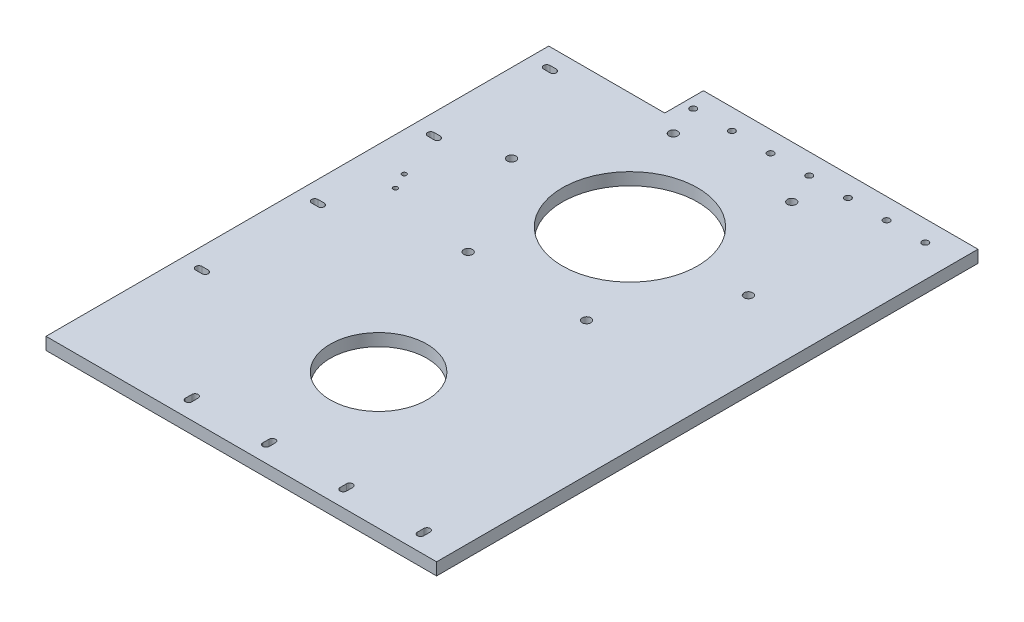
SolidWorks part; units mm, degrees
ref_plane "Front Plane" through (0, 0, 0) normal (0, 0, 1) x (1, 0, 0)
ref_plane "Top Plane" through (0, 0, 0) normal (0, 1, 0) x (1, 0, 0)
ref_plane "Right Plane" through (0, 0, 0) normal (1, 0, 0) x (0, 0, -1)
sketch "Sketch1" plane through (0, 0, 0) normal (0, 1, 0) x (1, 0, 0)
  line L3 (-71, 140) -> (71, 140)
  line L4 (71, -140) -> (71, 140)
  line L5 (0, 140) -> (0, -135) construction
  line L6 (0, 0) -> (71, 0) construction
  line L10 (-71, 140) -> (-71, 120)
  line L11 (-71, 120) -> (-131, 120)
  line L12 (-131, 120) -> (-131, -140)
  line L13 (-131, -140) -> (71, -140)
  point P0 (0, 0)
  dimension "D1" = 280
  dimension "D2" = 20
  dimension "D3" = 202
  dimension "D4" = 60
extrude "Boss-Extrude1" add sketch "Sketch1" along normal blind 6.35
sketch "Sketch2" plane through (0, 6.35, 0) normal (0, 1, 0) x (1, 0, 0)
  line L1 (0, 140) -> (0, -140) construction
  line L2 (71, 140) -> (-71, 140) construction
  line L3 (-131, -140) -> (71, -140) construction
  circle A0 centre (0, -65) radius 41.5 construction
  circle A1 centre (0, -23.5) radius 2.25
  circle A2 centre (29.3449, -35.6551) radius 2.25
  circle A3 centre (41.5, -65) radius 2.25
  circle A4 centre (29.3449, -94.3449) radius 2.25
  circle A5 centre (0, -106.5) radius 2.25
  circle A6 centre (-29.3449, -94.3449) radius 2.25
  circle A7 centre (-41.5, -65) radius 2.25
  circle A8 centre (-29.3449, -35.6551) radius 2.25
  circle A9 centre (0, -65) radius 80 construction
  circle A10 centre (0, -65) radius 30
  point P22 (0, -65)
  dimension "D1" = 83
  dimension "D2" = 4.5
  dimension "D4" = 160
  dimension "D6" = 60
  dimension "D5" = 75
  dimension "D3" = 8
extrude "Cut-Extrude1" [suppressed] cut sketch "Sketch2" against normal through all
sketch "Sketch6" [suppressed] plane through (0, 6.35, 0) normal (0, 1, 0) x (1, 0, 0)
  line L0 (0, -65) -> (-38.9712, -46.8274) construction
  line L1 (0, -65) -> (0, -23.5) construction
  line L2 (-40.9787, -51.1324) -> (-36.9638, -42.5225) construction
  line L3 (-36.9638, -42.5225) -> (-27.9007, -46.7486) construction
  circle A0 centre (0, -65) radius 30 construction
  circle A1 centre (-36.9638, -42.5225) radius 0.85
  circle A2 centre (-40.9787, -51.1324) radius 0.85
  circle A5 centre (-29.9082, -51.0536) radius 0.85
  point P7 (-38.9712, -46.8274)
  dimension "D4" = 1.7
  dimension "D5" = 10
  dimension "D7" = 10
  dimension "D6" = 1.7
  dimension "D1" = 43
  dimension "D2" = 9.5
  dimension "D3" = 65
extrude "Cut-Extrude5" [suppressed] cut sketch "Sketch6" against normal through all
sketch "Sketch8" [suppressed] plane through (0, 6.35, 0) normal (0, 1, 0) x (1, 0, 0)
  line L1 (71, 140) -> (-71, 140) construction
  line L2 (65, -20.6305) -> (65, 140) construction
  line L3 (71, -140) -> (71, 140) construction
  line L5 (45, 41.8036) -> (45, 140) construction
  circle A0 centre (0, 65) radius 25
  circle A1 centre (0, -65) radius 30 construction
  dimension "D1" = 130
  dimension "D2" = 50
  dimension "D3" = 6
  dimension "D4" = 20
extrude "Cut-Extrude9" [suppressed] cut sketch "Sketch8" against normal through all
sketch "Sketch9" plane through (0, 0, 0) normal (0, -1, 0) x (-1, 0, 0)
  circle A1 centre (45.6, 129.325) radius 1.65
  circle A2 centre (5.6, 129.325) radius 1.65
  circle A3 centre (-34.4, 129.325) radius 1.65
  circle A4 centre (65.6, 129.325) radius 1.65
  circle A5 centre (25.6, 129.325) radius 1.65
  circle A6 centre (-14.4, 129.325) radius 1.65
  circle A7 centre (-54.4, 129.325) radius 1.65
extrude "Cut-Extrude10" cut sketch "Sketch9" against normal blind 30
sketch "Sketch10" plane through (0, 0, 0) normal (0, -1, 0) x (1, 0, 0)
  line L0 (-121.975, 10) -> (-118.675, 10) construction
  line L3 (-121.975, 11.65) -> (-118.675, 11.65)
  line L4 (-121.975, 8.35) -> (-118.675, 8.35)
  line L5 (-121.975, 70) -> (-118.675, 70) construction
  line L6 (-121.975, 71.65) -> (-118.675, 71.65)
  line L7 (-121.975, 68.35) -> (-118.675, 68.35)
  line L8 (-121.975, -50) -> (-118.675, -50) construction
  line L9 (-121.975, -48.35) -> (-118.675, -48.35)
  line L10 (-121.975, -51.65) -> (-118.675, -51.65)
  line L11 (-121.975, -110) -> (-118.675, -110) construction
  line L12 (-121.975, -108.35) -> (-118.675, -108.35)
  line L13 (-121.975, -111.65) -> (-118.675, -111.65)
  circle A0 centre (-120.325, -110) radius 1.65
  circle A1 centre (-120.325, -50) radius 1.65
  circle A2 centre (-120.325, 10) radius 1.65
  circle A3 centre (-120.325, 70) radius 1.65
  arc A6 (-121.975, 11.65) -> (-121.975, 8.35) centre (-121.975, 10) ccw
  arc A7 (-118.675, 8.35) -> (-118.675, 11.65) centre (-118.675, 10) ccw
  arc A8 (-121.975, 71.65) -> (-121.975, 68.35) centre (-121.975, 70) ccw
  arc A9 (-118.675, 68.35) -> (-118.675, 71.65) centre (-118.675, 70) ccw
  arc A10 (-121.975, -48.35) -> (-121.975, -51.65) centre (-121.975, -50) ccw
  arc A11 (-118.675, -51.65) -> (-118.675, -48.35) centre (-118.675, -50) ccw
  arc A12 (-121.975, -108.35) -> (-121.975, -111.65) centre (-121.975, -110) ccw
  arc A13 (-118.675, -111.65) -> (-118.675, -108.35) centre (-118.675, -110) ccw
  point P14 (-120.325, 10)
  point P21 (-120.325, 70)
  point P28 (-120.325, -50)
  point P35 (-120.325, -110)
  dimension "D1" = 3.3
  dimension "D2" = 3.3
  dimension "D3" = 3.3
  dimension "D4" = 3.3
  dimension "D5" = 1.65
  dimension "D6" = 1.65
  dimension "D7" = 1.65
  dimension "D8" = 1.65
sketch "Sketch11" plane through (0, 6.35, 0) normal (0, 1, 0) x (1, 0, 0)
  line L0 (71, -127.15) -> (-131, -127.15) construction
  line L1 (71, -140) -> (71, 140) construction
  line L2 (456.625, -127.15) -> (-127.825, -127.15) construction
  line L3 (-131, 120) -> (-131, -140) construction
  line L4 (71, -132.85) -> (-131, -132.85) construction
  line L5 (456.625, -132.85) -> (-127.825, -132.85) construction
  line L6 (-65.6, 129.325) -> (-65.6, -130.005) construction
  line L7 (-65.6, -130.005) -> (71, -130) construction
  line L8 (456.625, -130) -> (-127.825, -130) construction
  line L9 (-25.6, 129.325) -> (-25.6, -130.0035) construction
  line L10 (14.4, 129.325) -> (14.4, -130.0021) construction
  line L11 (54.4, 129.325) -> (54.4, -130.0006) construction
  line L12 (-65.6, -128.355) -> (-65.6, -131.655) construction
  line L13 (-63.95, -128.355) -> (-63.95, -131.655)
  line L14 (-67.25, -128.355) -> (-67.25, -131.655)
  line L15 (-25.6, -128.3535) -> (-25.6, -131.6535) construction
  line L16 (-23.95, -128.3535) -> (-23.95, -131.6535)
  line L17 (-27.25, -128.3535) -> (-27.25, -131.6535)
  line L18 (14.4, -128.3521) -> (14.4, -131.6521) construction
  line L19 (16.05, -128.3521) -> (16.05, -131.6521)
  line L20 (12.75, -128.3521) -> (12.75, -131.6521)
  line L21 (54.4, -128.3506) -> (54.4, -131.6506) construction
  line L22 (56.05, -128.3506) -> (56.05, -131.6506)
  line L23 (52.75, -128.3506) -> (52.75, -131.6506)
  circle A0 centre (-65.6, -130.005) radius 1.65 construction
  circle A1 centre (-25.6, -130.0035) radius 1.65 construction
  circle A2 centre (14.4, -130.0021) radius 1.65 construction
  circle A3 centre (54.4, -130.0006) radius 1.65 construction
  arc A4 (-63.95, -128.355) -> (-67.25, -128.355) centre (-65.6, -128.355) ccw
  arc A5 (-67.25, -131.655) -> (-63.95, -131.655) centre (-65.6, -131.655) ccw
  arc A6 (-23.95, -128.3535) -> (-27.25, -128.3535) centre (-25.6, -128.3535) ccw
  arc A7 (-27.25, -131.6535) -> (-23.95, -131.6535) centre (-25.6, -131.6535) ccw
  arc A8 (16.05, -128.3521) -> (12.75, -128.3521) centre (14.4, -128.3521) ccw
  arc A9 (12.75, -131.6521) -> (16.05, -131.6521) centre (14.4, -131.6521) ccw
  arc A10 (56.05, -128.3506) -> (52.75, -128.3506) centre (54.4, -128.3506) ccw
  arc A11 (52.75, -131.6506) -> (56.05, -131.6506) centre (54.4, -131.6506) ccw
  point P33 (-65.6, -130.005)
  point P39 (-25.6, -130.0035)
  point P46 (14.4, -130.0021)
  point P53 (54.4, -130.0006)
  dimension "D2" = 3.3
  dimension "D1" = 259.33
extrude "Cut-Extrude12" cut sketch "Sketch11" against normal blind 30
extrude "Cut-Extrude13" cut sketch "Sketch10" against normal blind 10 contours A0 | L13 A13 L12 A0 | L12 A12 L13 A0 | L9 A10 L10 A1 | A1 | L10 A11 L9 A1 | L3 A6 L4 A2 | A2 | L4 A7 L3 A2 | L6 A8 L7 A3 | A3 | L7 A9 L6 A3 region at (-122.4459, 0, 10) region at (-118.2041, 0, 10) region at (-120.325, 0, 10) region at (-122.4459, 0, 70) region at (-118.2041, 0, 70) region at (-120.325, 0, 70) region at (-122.4459, 0, -50) region at (-118.2041, 0, -50) region at (-120.325, 0, -50) region at (-122.4459, 0, -110) region at (-118.2041, 0, -110) region at (-120.325, 0, -110)
sketch "Sketch12" plane through (0, 6.35, 0) normal (0, 1, 0) x (1, 0, 0)
  line L0 (-131, -140) -> (71, -140) construction
  line L1 (71, -140) -> (71, 140) construction
  circle A0 centre (-29, 60) radius 35
  dimension "D1" = 70
  dimension "D2" = 200
  dimension "D3" = 100
extrude "Cut-Extrude14" cut sketch "Sketch12" against normal through all
sketch "Sketch13" plane through (0, 6.35, 0) normal (0, 1, 0) x (1, 0, 0)
  line L0 (-96.5, 60) -> (-84, 60) construction
  circle A2 centre (-29, 60) radius 67.5 construction
  circle A3 centre (-90.25, 60) radius 2.25
  circle A4 centre (-59.625, 113.0441) radius 2.25
  circle A5 centre (-29, 60) radius 67.5 construction
  circle A6 centre (1.625, 113.0441) radius 2.25
  circle A7 centre (-29, 60) radius 67.5 construction
  circle A8 centre (32.25, 60) radius 2.25
  circle A9 centre (-29, 60) radius 67.5 construction
  circle A10 centre (1.625, 6.9559) radius 2.25
  circle A11 centre (-29, 60) radius 67.5 construction
  circle A12 centre (-59.625, 6.9559) radius 2.25
  circle A13 centre (-29, 60) radius 67.5 construction
  circle A14 centre (-29, 60) radius 55 construction
  circle A15 centre (-29, 60) radius 35 construction
  point P25 (-29, 60)
  dimension "D1" = 135
  dimension "D2" = 4.5
  dimension "D3" = 6
  dimension "D4" = 110
extrude "Cut-Extrude15" cut sketch "Sketch13" against normal through all
sketch "Sketch14" plane through (0, 6.35, 0) normal (0, 1, 0) x (1, 0, 0)
  circle A0 centre (-29, -70) radius 25
  circle A1 centre (-29, 60) radius 35 construction
  circle A2 centre (-29, 60) radius 35 construction
  dimension "D1" = 50
  dimension "D2" = 130
extrude "Cut-Extrude16" cut sketch "Sketch14" against normal blind 10
sketch "Sketch15" plane through (0, 6.35, 0) normal (0, 1, 0) x (1, 0, 0)
  line L0 (-111.0245, 25.2989) -> (-106.9837, 16.7011) construction
  line L1 (-94.5, -140) -> (-94.5, 120) construction
  line L2 (-131, 120) -> (-131, -140) construction
  line L3 (-71, 120) -> (-131, 120) construction
  line L4 (-131, -140) -> (71, -140) construction
  line L5 (-94.5, 26) -> (-131, 26) construction
  line L6 (-94.5, 16) -> (-131, 16) construction
  line L7 (-131, 26) -> (-131, 16) construction
  line L8 (-99.1997, 26) -> (-94.5, 16) construction
  circle A0 centre (-111.0245, 25.2989) radius 1.175
  circle A1 centre (-106.9837, 16.7011) radius 1.175
  circle A2 centre (-29, 60) radius 78 construction
  circle A3 centre (-29, 60) radius 35 construction
  point P18 (-109.0041, 21)
  point P19 (-131, 21)
  dimension "D1" = 2.35
  dimension "D2" = 9.5
  dimension "D3" = 11
  dimension "D7" = 156
  dimension "D4" = 36.5
  dimension "D5" = 94
  dimension "D6" = 10
extrude "Cut-Extrude17" cut sketch "Sketch15" against normal blind 10
